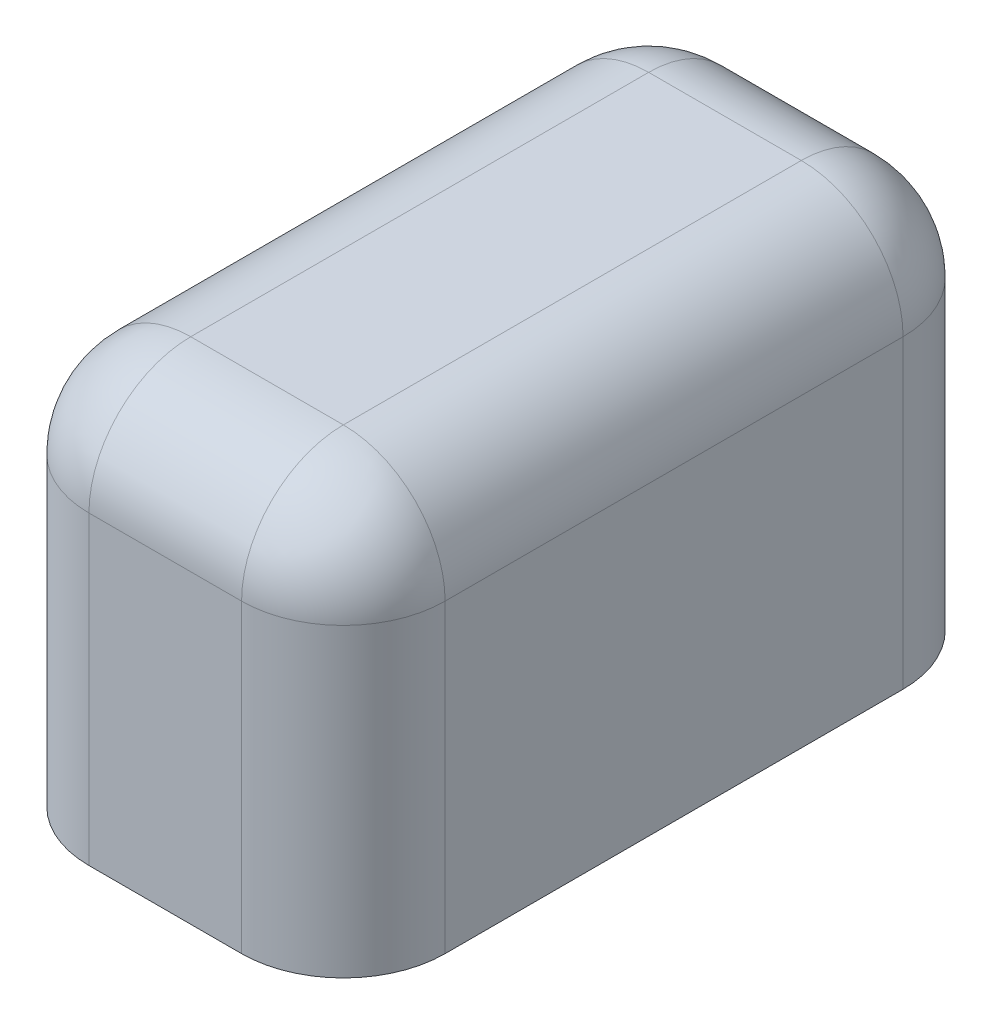
SolidWorks part; units mm, degrees
ref_plane "Front Plane" through (0, 0, 0) normal (0, 0, 1) x (1, 0, 0)
ref_plane "Top Plane" through (0, 0, 0) normal (0, 1, 0) x (1, 0, 0)
ref_plane "Right Plane" through (0, 0, 0) normal (1, 0, 0) x (0, 0, -1)
sketch "Sketch1" plane through (0, 0, 0) normal (1, 0, 0) x (0, 0, -1)
  line L1 (0, 0) -> (16.51, 0)
  line L2 (0, 0) -> (0, 10.16)
  line L3 (0, 10.16) -> (16.51, 10.16)
  line L4 (16.51, 0) -> (16.51, 10.16)
  dimension "D1" = 10.16
  dimension "D2" = 16.51
extrude "Boss-Extrude1" add sketch "Sketch1" along normal mid plane 8.89
fillet "Fillet1" radius 2.54 8 edges at (0, 10.16, -16.51) (-4.445, 10.16, -8.255) (0, 10.16, 0) (4.445, 10.16, -8.255) (4.445, 5.08, -16.51) (-4.445, 5.08, -16.51) (-4.445, 5.08, 0) (4.445, 5.08, 0)
